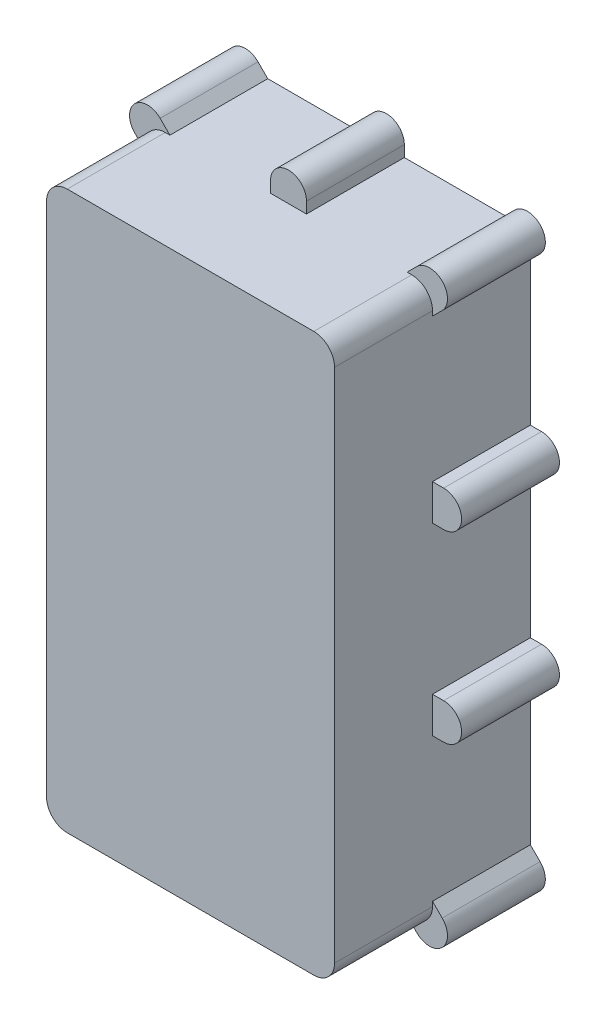
SolidWorks part; units mm, degrees
material "ABS"
ref_plane "X-Y Datum" through (0, 0, 0) normal (0, 0, 1) x (1, 0, 0)
ref_plane "X-Z Datum" through (0, 0, 0) normal (0, 1, 0) x (1, 0, 0)
ref_plane "Y-Z Datum" through (0, 0, 0) normal (1, 0, 0) x (0, 0, -1)
sketch "Sketch1" plane through (0, 0, 0) normal (0, 0, 1) x (1, 0, 0)
  line L0 (1.8162, 48.1563) -> (125.4513, 48.1563) construction
  line L1 (24.3593, 48.1563) -> (24.3593, 120.2923) construction
  line L3 (24.3593, 120.2923) -> (125.4513, 120.2923) construction
  line L8 (125.4513, 48.1563) -> (125.4513, 120.2923) construction
  line L33 (24.3593, 120.2923) -> (1.8162, 120.2923) construction
  line L34 (24.3593, 120.2923) -> (24.3593, 48.1563) construction
  line L35 (63.6337, 48.1563) -> (63.6337, 43.0763) construction
  line L36 (1.8162, 120.2923) -> (1.8162, 48.1563) construction
  line L41 (24.3593, 120.2923) -> (23.7243, 120.2923) construction
  line L42 (24.3593, 120.2923) -> (24.3593, 122.8323) construction
  line L44 (27.5343, 14.7553) -> (27.5343, 43.0763) construction
  line L45 (125.4513, 120.2923) -> (127.9913, 120.2923) construction
  line L46 (27.5343, 14.7553) -> (125.4513, 14.7553) construction
  line L47 (23.7243, 122.8323) -> (127.9913, 122.8323)
  line L48 (23.7243, 122.8323) -> (23.7243, -21.9477)
  line L49 (23.7243, -21.9477) -> (127.9913, -21.9477)
  line L50 (127.9913, 122.8323) -> (127.9913, -21.9477)
  line L51 (125.4513, 14.7553) -> (125.4513, 43.0763) construction
  line L52 (27.5343, 43.0763) -> (125.4513, 43.0763) construction
  line L53 (23.7243, 120.2923) -> (23.7243, 48.1563) construction
  circle A17 centre (30.4553, 114.1963) radius 2.1 construction
  circle A18 centre (119.8633, 115.2123) radius 2.1 construction
  circle A19 centre (119.6813, 54.2533) radius 2.1 construction
  circle A20 centre (29.4393, 53.2363) radius 2.1 construction
  circle A26 centre (31.9793, 18.4383) radius 2.1 construction
  circle A27 centre (31.9793, 39.3933) radius 2.1 construction
  circle A28 centre (120.6193, 28.8183) radius 2.1 construction
sketch "Sketch2" plane through (0, 0, 0) normal (0, 0, 1) x (1, 0, 0)
  line L4 (55.176, 122.8323) -> (127.9913, 122.8323)
  line L6 (55.176, 48.5244) -> (55.176, 50.9244) construction
  line L7 (55.176, -21.05) -> (127.9913, -21.05)
  line L8 (127.9913, 122.8323) -> (127.9913, -21.05)
  line L9 (55.176, 110.2103) -> (127.9913, -21.05) construction
  line L10 (55.176, -8.428) -> (127.9913, 122.8323) construction
  line L11 (55.176, 50.9244) -> (55.176, -21.05)
  line L12 (55.176, 50.9244) -> (55.176, 122.8323)
  circle A7 centre (88.0827, 6.45) radius 27.5
  circle A8 centre (88.0294, 95.3501) radius 27.5
  circle A9 centre (98.216, 50.8911) radius 6.477
  circle A10 centre (77.896, 50.9089) radius 6.477
  circle A11 centre (121.5143, 31.8208) radius 6.477
  circle A12 centre (115.996, 50.8756) radius 2.4
  circle A13 centre (55.176, 50.9244) radius 2.4
  point P14 (88.0827, 50.8911)
sketch "Sketch3" plane through (0, 0, 0) normal (0, 0, 1) x (1, 0, 0)
  line L7 (0, 0) -> (76.2, 0)
  line L10 (0, 0) -> (0, 158.75)
  line L11 (0, 158.75) -> (76.2, 158.75)
  line L12 (76.2, 0) -> (76.2, 158.75)
  dimension "D1" = 158.75
  dimension "D2" = 76.2
extrude "Boss-Extrude1" add sketch "Sketch3" along normal blind 53.975
shell "Shell1" thickness 6 removed face at (38.1, 79.375, 0) outward yes
fillet "Fillet1" radius 5.334 4 edges at (76.2, 158.75, 26.9875) (76.2, 0, 26.9875) (0, 0, 26.9875) (0, 158.75, 26.9875)
fillet "Fillet2" radius 6.35 4 edges at (-6, -6, 29.9875) (-6, 164.75, 29.9875) (82.2, 164.75, 29.9875) (82.2, -6, 29.9875)
sketch "Sketch6" plane through (0, 0, 0) normal (0, 0, -1) x (-1, 0, 0)
  line L8 (-5.334, 163.0327) -> (-70.866, 163.0327)
  line L9 (-80.4827, 153.416) -> (-80.4827, 5.334)
  line L10 (-70.866, -4.2827) -> (-5.334, -4.2827)
  line L11 (4.2827, 5.334) -> (4.2827, 153.416)
  line L12 (-79.2, 153.416) -> (-79.2, 5.334)
  line L13 (-70.866, -3) -> (-5.334, -3)
  line L14 (3, 5.334) -> (3, 153.416)
  line L15 (-5.334, 161.75) -> (-70.866, 161.75)
  line L16 (-79.2, 153.416) -> (-79.2, 5.334) construction
  line L17 (-70.866, -3) -> (-5.334, -3) construction
  line L18 (3, 5.334) -> (3, 153.416) construction
  line L19 (-5.334, 161.75) -> (-70.866, 161.75) construction
  line L20 (-77.9173, 153.416) -> (-77.9173, 5.334)
  line L21 (-70.866, -1.7173) -> (-5.334, -1.7173)
  line L22 (1.7173, 5.334) -> (1.7173, 153.416)
  line L23 (-5.334, 160.4673) -> (-70.866, 160.4673)
  arc A8 (-70.866, 163.0327) -> (-80.4827, 153.416) centre (-70.866, 153.416) ccw
  arc A9 (-80.4827, 5.334) -> (-70.866, -4.2827) centre (-70.866, 5.334) ccw
  arc A10 (-5.334, -4.2827) -> (4.2827, 5.334) centre (-5.334, 5.334) ccw
  arc A11 (4.2827, 153.416) -> (-5.334, 163.0327) centre (-5.334, 153.416) ccw
  arc A12 (-70.866, 161.75) -> (-79.2, 153.416) centre (-70.866, 153.416) ccw
  arc A13 (-79.2, 5.334) -> (-70.866, -3) centre (-70.866, 5.334) ccw
  arc A14 (-5.334, -3) -> (3, 5.334) centre (-5.334, 5.334) ccw
  arc A15 (3, 153.416) -> (-5.334, 161.75) centre (-5.334, 153.416) ccw
  arc A16 (-70.866, 161.75) -> (-79.2, 153.416) centre (-70.866, 153.416) ccw construction
  arc A17 (-79.2, 5.334) -> (-70.866, -3) centre (-70.866, 5.334) ccw construction
  arc A18 (-5.334, -3) -> (3, 5.334) centre (-5.334, 5.334) ccw construction
  arc A19 (3, 153.416) -> (-5.334, 161.75) centre (-5.334, 153.416) ccw construction
  arc A20 (-77.9173, 5.334) -> (-70.866, -1.7173) centre (-70.866, 5.334) ccw
  arc A21 (-5.334, -1.7173) -> (1.7173, 5.334) centre (-5.334, 5.334) ccw
  arc A22 (1.7173, 153.416) -> (-5.334, 160.4673) centre (-5.334, 153.416) ccw
  arc A23 (-70.866, 160.4673) -> (-77.9173, 153.416) centre (-70.866, 153.416) ccw
  dimension "D4" = 7.0513
  dimension "D5" = 2.5654
  dimension "D1" = 3
  dimension "D2" = 1.2827
  dimension "D3" = 1.2827
extrude "Cut-Extrude1" cut sketch "Sketch6" against normal blind 1.2446
fillet "Fillet3" radius 0.254 16 edges at (-4.2827, 79.375, 1.2446) (-1.466, -1.466, 1.2446) (38.1, -4.2827, 1.2446) (77.666, -1.466, 1.2446) (80.4827, 79.375, 1.2446) (77.666, 160.216, 1.2446) (38.1, 163.0327, 1.2446) (-1.466, 160.216, 1.2446) (75.852, 158.402, 1.2446) (77.9173, 79.375, 1.2446) (75.852, 0.348, 1.2446) (38.1, -1.7173, 1.2446) (0.348, 0.348, 1.2446) (-1.7173, 79.375, 1.2446) (0.348, 158.402, 1.2446) (38.1, 160.4673, 1.2446)
fillet "Fillet4" radius 0.127 16 edges at (75.852, 158.402, 0) (38.1, 160.4673, 0) (0.348, 158.402, 0) (-1.7173, 79.375, 0) (0.348, 0.348, 0) (38.1, -1.7173, 0) (75.852, 0.348, 0) (77.666, 160.216, 0) (38.1, 163.0327, 0) (-1.466, 160.216, 0) (-4.2827, 79.375, 0) (-1.466, -1.466, 0) (38.1, -4.2827, 0) (77.666, -1.466, 0) (77.9173, 79.375, 0) (80.4827, 79.375, 0)
sketch "Sketch7" plane through (0, 0, 53.975) normal (0, 0, -1) x (-1, 0, 0)
  line L0 (-76.2, 34.925) -> (0, 34.925)
  line L1 (-76.2, 5.334) -> (-76.2, 153.416) construction
  line L2 (0, 153.416) -> (0, 5.334) construction
  line L3 (-76.2, 37.425) -> (0, 37.425)
  line L4 (-5.334, 0) -> (-70.866, 0) construction
  line L5 (-76.2, 34.925) -> (-76.2, 37.425)
  line L6 (0, 34.925) -> (0, 37.425)
  dimension "D2" = 34.925
  dimension "D1" = 2.5
extrude "Boss-Extrude2" add sketch "Sketch7" along normal up to surface (53.975 mm away) up to face at (38.1, 79.375, 0)
sketch "Sketch8" plane through (0, 0, 0) normal (0, 0, -1) x (-1, 0, 0)
  line L0 (-5.334, 5.334) -> (5.0914, -5.0914)
  line L1 (-1.7782, -6) -> (1.2023, -8.9805)
  line L2 (-0.35, -6) -> (-75.85, -6) construction
  line L3 (-5.334, -4.2827) -> (-5.334, -4.4097)
  line L4 (4.4097, 5.334) -> (4.2827, 5.334)
  line L5 (-5.334, -4.2827) -> (-5.334, -4.4097)
  line L6 (4.4097, 5.334) -> (4.2827, 5.334)
  line L7 (6, 1.7782) -> (8.9805, -1.2023)
  line L8 (6, 158.4) -> (6, 0.35) construction
  line L9 (-38.1, -6) -> (-38.1, 164.75) construction
  line L10 (-75.85, 164.75) -> (-0.35, 164.75) construction
  line L11 (-82.2, 79.375) -> (6, 79.375) construction
  line L12 (-82.2, 0.35) -> (-82.2, 158.4) construction
  circle A0 centre (5.0914, -5.0914) radius 3.025
  circle A1 centre (5.0914, -5.0914) radius 5.5
  arc A3 (-5.334, -4.4097) -> (4.4097, 5.334) centre (-5.334, 5.334) ccw
  arc A4 (-5.334, -4.2827) -> (4.2827, 5.334) centre (-5.334, 5.334) ccw
  arc A5 (-5.334, -4.4097) -> (4.4097, 5.334) centre (-5.334, 5.334) ccw
  arc A6 (-5.334, -4.2827) -> (4.2827, 5.334) centre (-5.334, 5.334) ccw
  point P6 (1.5558, -1.5558)
  arc M11 (4.4097, 5.334) -> (-5.334, -4.4097) centre (-5.334, 5.334) cw
  line M14 (-75.85, -6) -> (-0.35, -6)
  arc M15 (-0.35, -6) -> (6, 0.35) centre (-0.35, 0.35) ccw
  line M16 (6, 0.35) -> (6, 158.4)
  dimension "D1" = 6.05
  dimension "D4" = 11
  dimension "D3" = 5
  dimension "D2" = 0
extrude "Boss-Extrude3" add sketch "Sketch8" against normal blind 29.972 contours A1 A0 M15 | A1 L1 M15 M14 | A1 L7 M16 M15 | A0 M15 | L0 A0 M15 | A0 L0 M15 | A1 A0 L0 M11 M15 | A1 L0 A0 M15 M11 region at (-3.9532, -1.0787, 0) region at (-1.0787, -3.9532, 0) region at (-4.2457, -2.9327, 0) region at (-2.9327, -4.2457, 0) region at (-6.789, 0.5448, 0) region at (-7.5393, -0.3393, 0) region at (0.5448, -6.789, 0) region at (-5.4552, -5.4552, 0)
sketch "Sketch9" plane through (0, 0, 0) normal (0, 0, -1) x (-1, 0, 0)
  circle A0 centre (5.0914, -5.0914) radius 3.025 construction
  circle A1 centre (5.0914, -5.0914) radius 3.025
  dimension "D1" = 6.05
extrude "Cut-Extrude2" cut sketch "Sketch9" against normal blind 9
ref_plane "Plane1" through (38.1, 0, 0) normal (-1, 0, 0) x (0, 0, 1)
ref_plane "Plane2" through (0, 79.375, 0) normal (0, -1, 0) x (-1, 0, 0)
mirror "Mirror1" about plane through (38.1, 0, 0) normal (-1, 0, 0) of "Cut-Extrude2", "Boss-Extrude3"
mirror "Mirror2" about plane through (0, 79.375, 0) normal (0, -1, 0) of "Cut-Extrude2", "Boss-Extrude3", "Mirror1"
sketch "Sketch10" plane through (0, 0, 0) normal (0, 0, -1) x (-1, 0, 0)
  line L0 (6, 79.375) -> (39.3327, 79.375) construction
  line L2 (6, 156.9718) -> (6, 1.7782) construction
  line L3 (6, 79.375) -> (6, 157.4914)
  line L4 (6, 107.569) -> (9.4097, 107.569) construction
  line L5 (4.4097, 153.416) -> (4.4097, 5.334) construction
  line L7 (9.4097, 113.069) -> (6, 113.069)
  line L9 (9.4097, 102.069) -> (6, 102.069)
  line L10 (9.4097, 45.681) -> (6, 45.681)
  line L11 (9.4097, 56.681) -> (6, 56.681)
  circle A4 centre (9.4097, 107.569) radius 3.025
  circle A5 centre (9.4097, 107.569) radius 5.5
  circle A6 centre (9.4097, 51.181) radius 3.025
  circle A7 centre (9.4097, 51.181) radius 5.5
  point P0 (5.0914, 163.8414)
  point P1 (5.0914, -5.0914)
  point P3 (-81.2914, -5.0914)
  line M14 (6, 1.7782) -> (6, 156.9718)
  line M21 (4.4097, 153.416) -> (4.4097, 5.334)
  dimension "D3" = 84.4664
  dimension "D4" = 6.05
  dimension "D5" = 11
  dimension "D1" = 168.9327
  dimension "D2" = 86.3827
  dimension "D6" = 5
  dimension "D7" = 28.194
  dimension "D8" = 56.2724
  dimension "D9" = 56.388
  dimension "D10" = 56.2724
extrude "Boss-Extrude4" add sketch "Sketch10" against normal blind 29.972 contours A7 A6 M14 | A7 L11 M14 | A7 M14 M21 | L10 A7 M14 | A6 | A5 L7 L3 | A5 L3 L9 | A5 A4 M14 | A5 M14 M21 | A4 region at (-6.833, 102.4167, 0) region at (-6.833, 56.3333, 0) region at (-5.2799, 107.569, 0) region at (-6.1416, 107.569, 0) region at (-13.1987, 54.97, 0) region at (-5.2799, 51.181, 0) region at (-6.833, 112.7213, 0) region at (-6.833, 46.0287, 0) region at (-9.4097, 107.569, 0) region at (-9.4097, 51.181, 0)
sketch "Sketch11" plane through (0, 0, 0) normal (0, 0, -1) x (-1, 0, 0)
  circle A0 centre (9.4097, 51.181) radius 3.025 construction
  circle A1 centre (9.4097, 107.569) radius 3.025 construction
  circle A2 centre (9.4097, 51.181) radius 3.025
  circle A3 centre (9.4097, 107.569) radius 3.025
  dimension "D1" = 6.05
extrude "Cut-Extrude3" cut sketch "Sketch11" against normal blind 9
mirror "Mirror3" about plane through (38.1, 0, 0) normal (-1, 0, 0) of "Cut-Extrude3", "Boss-Extrude4"
sketch "Sketch12" plane through (0, 0, 0) normal (0, 0, -1) x (-1, 0, 0)
  line L0 (-74.4218, -6) -> (-1.7782, -6)
  line L1 (-38.1, -6) -> (-38.1, -9.4097) construction
  line L2 (-5.334, -4.4097) -> (-70.866, -4.4097) construction
  line L3 (-43.6, -9.4097) -> (-43.6, -6)
  line L4 (-32.6, -9.4097) -> (-32.6, -6)
  circle A0 centre (-38.1, -9.4097) radius 3.025
  circle A1 centre (-38.1, -9.4097) radius 5.5
  point P15 (-81.2914, -5.0914)
  point P16 (5.0914, -5.0914)
  line M16 (-74.4218, -6) -> (-1.7782, -6)
  line M42 (-5.334, -4.4097) -> (-70.866, -4.4097)
  dimension "D2" = 6.05
  dimension "D4" = 11
  dimension "D1" = 43.1914
  dimension "D3" = 5
  dimension "D5" = 86.3827
extrude "Boss-Extrude5" add sketch "Sketch12" against normal blind 29.972 contours A1 L0 A0 M16 | A1 L0 L3 | A1 L4 L0 | A0 | L0 A1 M16 M42 region at (43.2523, -6.833, 0) region at (38.1, -5.2799, 0) region at (38.1, -6.1416, 0) region at (32.9477, -6.833, 0) region at (38.1, -9.4097, 0)
sketch "Sketch13" plane through (0, 0, 0) normal (0, 0, -1) x (-1, 0, 0)
  circle A0 centre (-38.1, -9.4097) radius 3.025 construction
  circle A1 centre (-38.1, -9.4097) radius 3.025
extrude "Cut-Extrude4" cut sketch "Sketch13" against normal blind 9
mirror "Mirror4" about plane through (0, 79.375, 0) normal (0, -1, 0) of "Cut-Extrude4", "Boss-Extrude5"
sketch "Sketch17" plane through (-6, 0, 0) normal (-1, 0, 0) x (0, 0, 1)
  line L0 (59.975, 158.4) -> (59.975, 0.35) construction
  line L1 (0, 37.425) -> (53.975, 37.425) construction
  line L2 (53.975, 34.925) -> (53.975, 5.334) construction
  circle A0 centre (38.385, 119.975) radius 9.525
  circle A1 centre (38.385, 119.975) radius 14.2875
  circle A2 centre (38.385, 20.1295) radius 6.35
  circle A3 centre (38.385, 20.1295) radius 10.795
  point P10 (53.975, 20.1295)
  dimension "D1" = 19.05
  dimension "D4" = 28.575
  dimension "D5" = 12.7
  dimension "D6" = 21.59
  dimension "D2" = 21.59
  dimension "D3" = 82.55
extrude "Cut-Extrude6" cut sketch "Sketch17" against normal blind 6 contours A0 | A2 region at (-6, 119.975, 38.385) region at (-6, 20.1295, 38.385)
sketch "Sketch18" plane through (0, 0, 0) normal (1, 0, 0) x (0, 0, -1)
  circle A0 centre (-38.385, 119.975) radius 14.2875 construction
  circle A1 centre (-38.385, 119.975) radius 14.2875
  circle A2 centre (-38.385, 20.1295) radius 10.795 construction
  circle A3 centre (-38.385, 20.1295) radius 10.795
extrude "Cut-Extrude7" cut sketch "Sketch18" against normal blind 3
